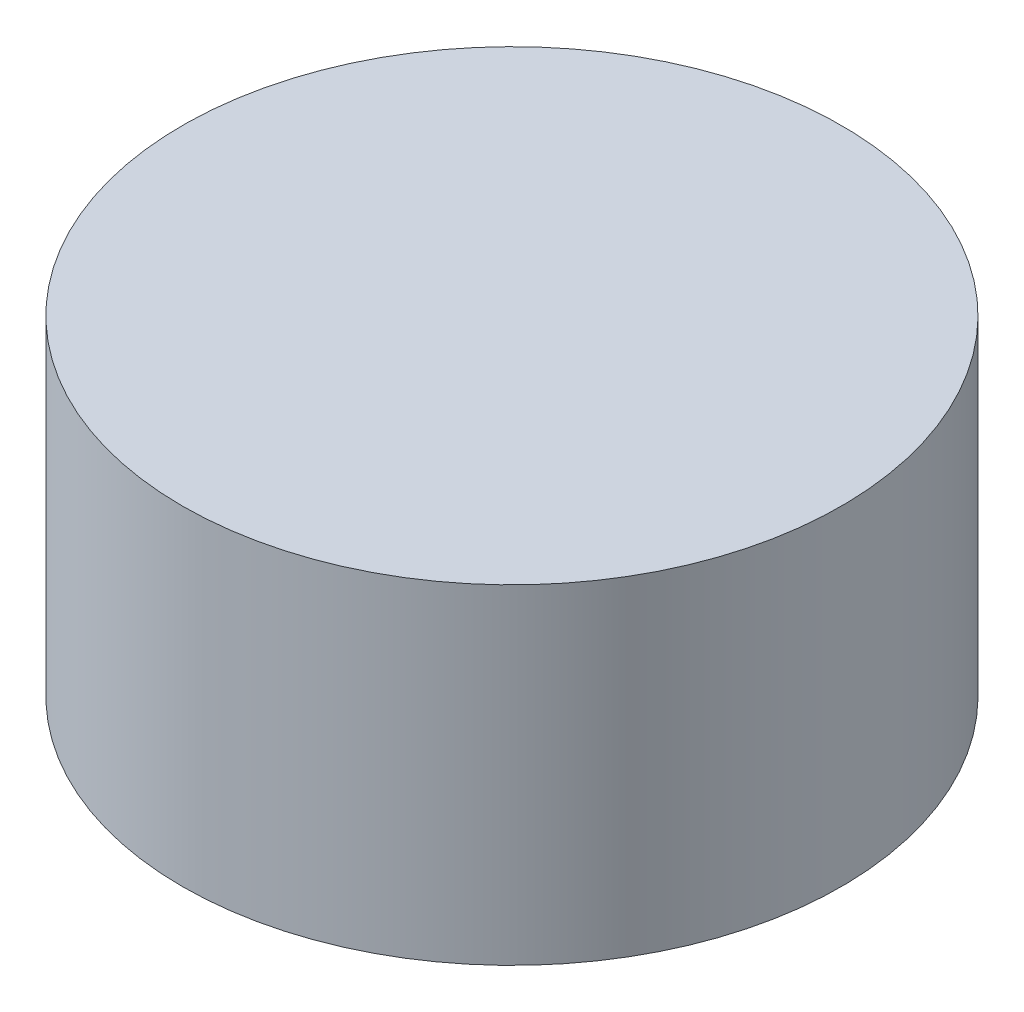
SolidWorks part; units mm, degrees
ref_plane "Front Plane" through (0, 0, 0) normal (0, 0, 1) x (1, 0, 0)
ref_plane "Top Plane" through (0, 0, 0) normal (0, 1, 0) x (1, 0, 0)
ref_plane "Right Plane" through (0, 0, 0) normal (1, 0, 0) x (0, 0, -1)
sketch "Sketch1" plane through (0, 0, 0) normal (0, 1, 0) x (1, 0, 0)
  line L0 (10.5, 0) -> (-10.5, 0) construction
  line L1 (-10.5, -3.2) -> (-10.5, 3.2)
  line L2 (-10.5, 3.2) -> (-12.2, 3.2)
  line L3 (-12.2, 3.2) -> (-12.2, -3.2)
  line L4 (-12.2, -3.2) -> (-10.5, -3.2)
  line L5 (0, -15) -> (0, 15) construction
  line L6 (12.2, 3.2) -> (12.2, -3.2)
  line L7 (10.5, 3.2) -> (12.2, 3.2)
  line L8 (10.5, -3.2) -> (10.5, 3.2)
  line L9 (12.2, -3.2) -> (10.5, -3.2)
  line L10 (-12.7, -3.7) -> (-10, -3.7)
  line L11 (-10, -3.7) -> (-10, 3.7)
  line L12 (-10, 3.7) -> (-12.7, 3.7)
  line L13 (-12.7, 3.7) -> (-12.7, -3.7)
  line L14 (12.7, 3.7) -> (12.7, -3.7)
  line L15 (10, 3.7) -> (12.7, 3.7)
  line L16 (10, -3.7) -> (10, 3.7)
  line L17 (12.7, -3.7) -> (10, -3.7)
  circle A0 centre (0, 0) radius 15
  point P6 (0, 0)
  point P9 (-10.5, 0)
  dimension "D1" = 30
  dimension "D2" = 21
  dimension "D3" = 6.4
  dimension "D4" = 1.7
  dimension "D5" = 0.5
extrude "Boss-Extrude1" add sketch "Sketch1" along normal blind 15 contours A0 L14 L17 L16 L15 L13 L12 L11 L10 | A0 region at (0, 0, 0)
sketch "Sketch2" plane through (0, 0, 0) normal (0, -1, 0) x (1, 0, 0)
  line L0 (0, 0) -> (-10.5, 0) construction
  line L1 (0, 15) -> (0, -15) construction
  line L2 (-10.5, 3.2) -> (-10.5, -3.2)
  line L3 (-10.5, 3.2) -> (-12.2, 3.2)
  line L4 (-10.5, -3.2) -> (-12.2, -3.2)
  line L5 (-12.2, 3.2) -> (-12.2, -3.2)
  line L6 (-10, 3.7) -> (-10, -3.7)
  line L7 (-10, -3.7) -> (-12.7, -3.7)
  line L8 (-12.7, 3.7) -> (-12.7, -3.7)
  line L9 (-10, 3.7) -> (-12.7, 3.7)
  line L10 (10, 3.7) -> (12.7, 3.7)
  line L11 (12.7, 3.7) -> (12.7, -3.7)
  line L12 (10, -3.7) -> (12.7, -3.7)
  line L13 (10, 3.7) -> (10, -3.7)
  circle A0 centre (0, 0) radius 15 construction
  point P8 (-10.5, 0)
  dimension "D1" = 6.4
  dimension "D2" = 1.7
  dimension "D3" = 21
  dimension "D4" = 0.5
extrude "Cut-Extrude1" cut sketch "Sketch2" against normal blind 5 contours L3 L5 L4 L2 | L6 L9 L8 L7 L5 L3 L2 L4 | L10 L13 L12 L11 region at (-11.35, 0, 0) region at (-10.0788, 0, 0) region at (11.35, 0, 0)
ref_axis "Axis1" through (0, 0, 0) along (0, 1, 0)
